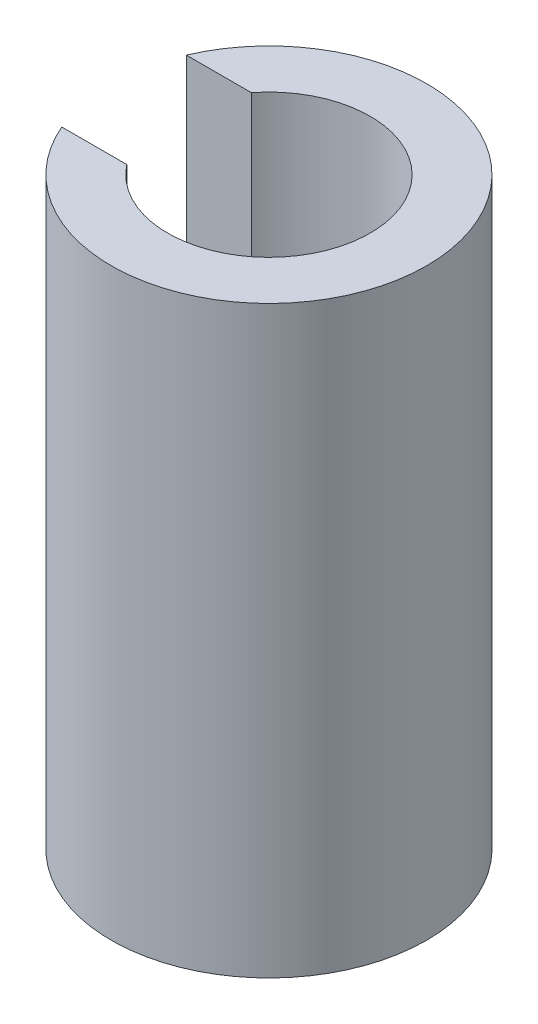
SolidWorks part; units mm, degrees
ref_plane "前基準面" through (0, 0, 0) normal (0, 0, 1) x (1, 0, 0)
ref_plane "上基準面" through (0, 0, 0) normal (0, 1, 0) x (1, 0, 0)
ref_plane "右基準面" through (0, 0, 0) normal (1, 0, 0) x (0, 0, -1)
ref_axis "基準軸1" through (0, -55, 0) along (0, 1, 0)
ref_axis "基準軸2" through (-88.99, 0, 0) along (1, 0, 0)
ref_axis "基準軸3" through (0, 0, 55) along (0, 0, -1)
sketch "草圖1" plane through (0, 0, 0) normal (0, 1, 0) x (1, 0, 0)
  circle A0 centre (0, 0) radius 2.6
  circle A1 centre (0, 0) radius 4.05
  dimension "D1" = 5.2
  dimension "D2" = 8.1
extrude "填料-伸長1" add sketch "草圖1" along normal blind 15
sketch "草圖2" plane through (0, 15, 0) normal (0, 1, 0) x (1, 0, 0)
  line L1 (-4.05, -1.5992) -> (-2.05, -1.5992)
  line L2 (-4.05, -1.5992) -> (-4.05, 1.5992)
  line L3 (-4.05, 1.5992) -> (-2.05, 1.5992)
  line L4 (-2.05, -1.5992) -> (-2.05, 1.5992)
  line L5 (-55, 0) -> (55, 0) construction
  circle A0 centre (0, 0) radius 4.05 construction
  circle A1 centre (0, 0) radius 2.6 construction
  point P4 (-2.05, 0)
  dimension "D1" = 2
extrude "除料-伸長1" cut sketch "草圖2" against normal blind 15
